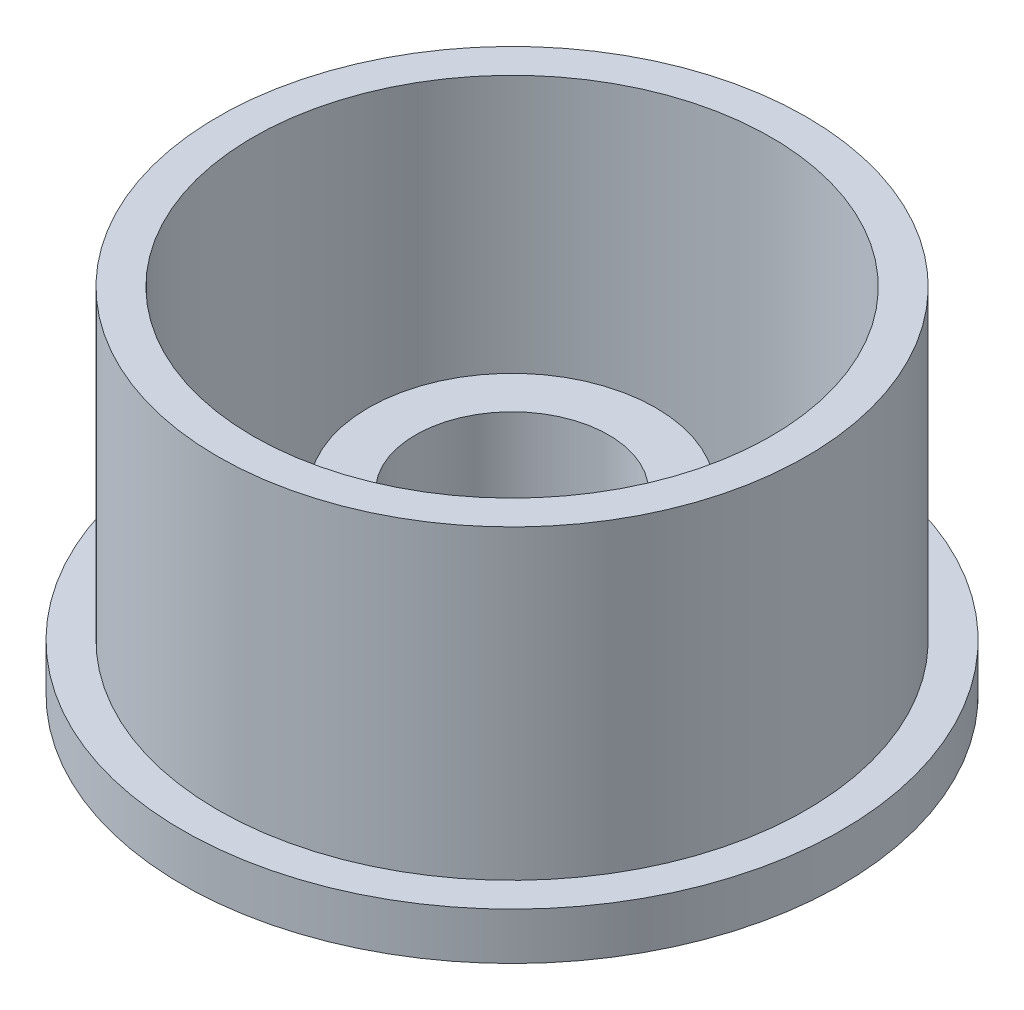
SolidWorks part; units mm, degrees
ref_plane "Front Plane" through (0, 0, 0) normal (0, 0, 1) x (1, 0, 0)
ref_plane "Top Plane" through (0, 0, 0) normal (0, 1, 0) x (1, 0, 0)
ref_plane "Right Plane" through (0, 0, 0) normal (1, 0, 0) x (0, 0, -1)
sketch "Sketch1" plane through (0, 0, 0) normal (0, 1, 0) x (1, 0, 0)
  circle A0 centre (0, 0) radius 12.5
  dimension "D1" = 25
extrude "Boss-Extrude1" add sketch "Sketch1" along normal blind 15
shell "Shell1" thickness 1.5 removed face at (0, 15, 12.5)
sketch "Sketch2" plane through (0, 1.5, 0) normal (0, 1, 0) x (1, 0, 0)
  circle A0 centre (0, 0) radius 4.1
  dimension "D1" = 8.2
extrude "Cut-Extrude1" cut sketch "Sketch2" against normal blind 20
sketch "Sketch3" plane through (0, 1.5, 0) normal (0, 1, 0) x (1, 0, 0)
  circle A0 centre (0, 0) radius 4.1
  circle A1 centre (0, 0) radius 6.1
  circle A2 centre (0, 0) radius 4.1 construction
  dimension "D1" = 2
extrude "Boss-Extrude2" add sketch "Sketch3" along normal offset from surface (6 mm away) 7.5 up to face at (0, 0, 4.1)
sketch "Sketch4" plane through (0, 0, 0) normal (0, -1, 0) x (1, 0, 0)
  circle A0 centre (0, 0) radius 11.5
  circle A1 centre (0, 0) radius 14
  circle A3 centre (0, 0) radius 12.5 construction
  dimension "D1" = 28
  dimension "D2" = 1
extrude "Boss-Extrude3" add sketch "Sketch4" against normal blind 2 separate body
combine bodies "Combine1" operation type add bodies to combine 103 104
